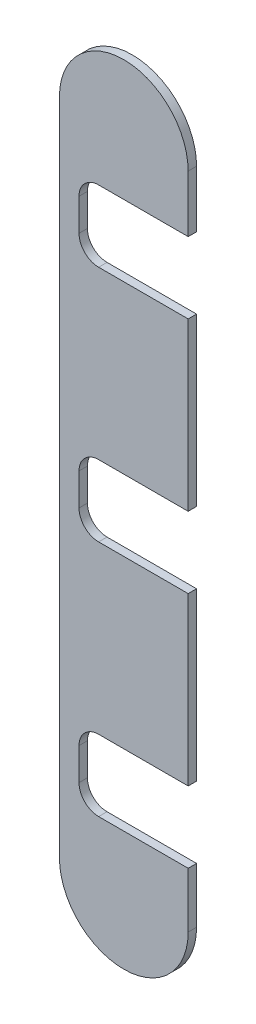
SolidWorks part; units mm, degrees
ref_plane "Front Plane" through (0, 0, 0) normal (0, 0, 1) x (1, 0, 0)
ref_plane "Top Plane" through (0, 0, 0) normal (0, 1, 0) x (1, 0, 0)
ref_plane "Right Plane" through (0, 0, 0) normal (1, 0, 0) x (0, 0, -1)
sketch "Sketch1" plane through (0, 0, 0) normal (0, 0, 1) x (1, 0, 0)
  line L1 (-43, 160.25) -> (-43, -75.25)
  line L2 (3, 160.25) -> (3, 139.9624)
  line L4 (-36, -30.0376) -> (3, -30.0376)
  line L5 (-36, -30.0376) -> (-36, -55.5)
  line L6 (-36, -55.5) -> (3, -55.5)
  line L8 (-36, 54.9624) -> (3, 54.9624)
  line L9 (-36, 54.9624) -> (-36, 29.5)
  line L10 (-36, 29.5) -> (3, 29.5)
  line L12 (-36, 139.9624) -> (3, 139.9624)
  line L13 (-36, 139.9624) -> (-36, 114.5)
  line L14 (-36, 114.5) -> (3, 114.5)
  line L24 (3, -55.5) -> (3, -75.25)
  line L25 (3, 29.5) -> (3, -30.0376)
  line L26 (3, 114.5) -> (3, 54.9624)
  arc A2 (3, 160.25) -> (-43, 160.25) centre (-20, 160.25) ccw
  arc A3 (-43, -75.25) -> (3, -75.25) centre (-20, -75.25) ccw
extrude "Boss-Extrude1" add sketch "Sketch1" along normal blind 3
fillet "Fillet1" radius 7 6 edges at (-36, 139.9624, 1.5) (-36, 114.5, 1.5) (-36, 54.9624, 1.5) (-36, 29.5, 1.5) (-36, -55.5, 1.5) (-36, -30.0376, 1.5)
